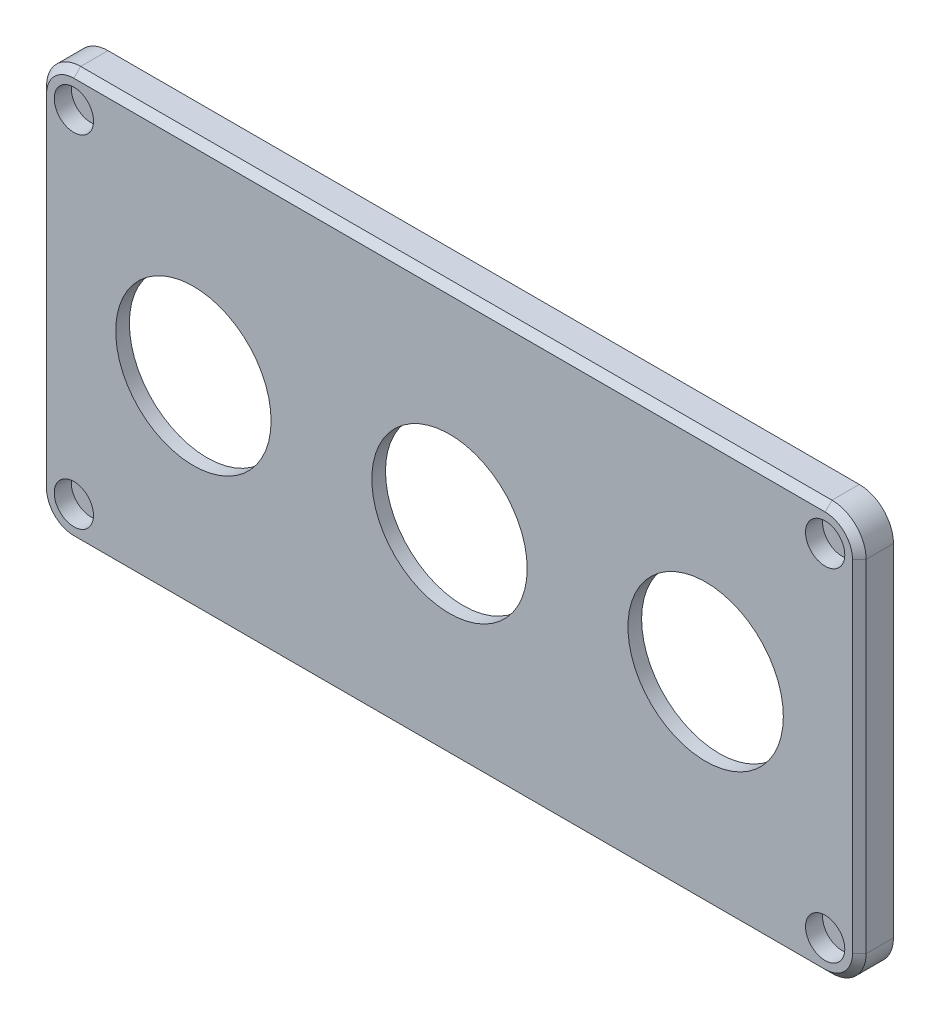
SolidWorks part; units mm, degrees
ref_plane "Front Plane" through (0, 0, 0) normal (0, 0, 1) x (1, 0, 0)
ref_plane "Top Plane" through (0, 0, 0) normal (0, 1, 0) x (1, 0, 0)
ref_plane "Right Plane" through (0, 0, 0) normal (1, 0, 0) x (0, 0, -1)
sketch "Sketch1" plane through (0, 0, 0) normal (0, 0, 1) x (1, 0, 0)
  line L1 (-60, 30) -> (60, 30)
  line L2 (-60, 30) -> (-60, -30)
  line L3 (-60, -30) -> (60, -30)
  line L4 (60, 30) -> (60, -30)
  line L5 (-60, 30) -> (60, -30) construction
  line L6 (-60, -30) -> (60, 30) construction
  point P0 (0, 0)
  dimension "D1" = 120
  dimension "D2" = 60
extrude "Boss-Extrude1" add sketch "Sketch1" along normal blind 5
sketch "Sketch2" plane through (0, 0, 5) normal (0, 0, 1) x (1, 0, 0)
  circle A0 centre (0, 0) radius 11.375
  circle A1 centre (37.5, 0) radius 11.375
  circle A2 centre (-37.5, 0) radius 11.375
  dimension "D3" = 22.75
  dimension "D1" = 75
  dimension "D2" = 37.5
extrude "Cut-Extrude1" cut sketch "Sketch2" against normal through all
fillet "Fillet1" radius 5 4 edges at (-60, -30, 2.5) (60, -30, 2.5) (60, 30, 2.5) (-60, 30, 2.5)
sketch "Sketch3" plane through (0, 0, 5) normal (0, 0, 1) x (1, 0, 0)
  circle A0 centre (-55, 25) radius 1.6
  circle A1 centre (55, 25) radius 1.6
  circle A2 centre (55, -25) radius 1.6
  circle A3 centre (-55, -25) radius 1.6
  dimension "D1" = 3.2
extrude "Cut-Extrude2" cut sketch "Sketch3" against normal through all
sketch "Sketch4" plane through (0, 0, 5) normal (0, 0, 1) x (1, 0, 0)
  circle A0 centre (-55, 25) radius 2.875
  circle A1 centre (55, 25) radius 2.875
  circle A2 centre (55, -25) radius 2.875
  circle A3 centre (-55, -25) radius 2.875
  dimension "D1" = 5.75
extrude "Cut-Extrude3" cut sketch "Sketch4" against normal blind 2.5
chamfer "Chamfer1" distance 1 angle 45 8 edges at (0, -30, 5) (58.5355, -28.5355, 5) (-58.5355, -28.5355, 5) (60, 0, 5) (-60, 0, 5) (58.5355, 28.5355, 5) (-58.5355, 28.5355, 5) (0, 30, 5)
sketch "Sketch5" plane through (0, 0, 0) normal (0, 0, -1) x (-1, 0, 0)
  circle A0 centre (-37.5, 0) radius 16
  circle A1 centre (0, 0) radius 16
  circle A2 centre (37.5, 0) radius 16
  dimension "D1" = 32
extrude "Cut-Extrude4" cut sketch "Sketch5" against normal blind 3
sketch "Sketch6" plane through (0, 0, 2.5) normal (0, 0, 1) x (1, 0, 0)
  circle A0 centre (-55, 25) radius 2.5
  circle A1 centre (55, 25) radius 2.5
  circle A2 centre (55, -25) radius 2.5
  circle A3 centre (-55, -25) radius 2.5
  dimension "D1" = 5
extrude "Boss-Extrude2" add sketch "Sketch6" against normal blind 0.15
